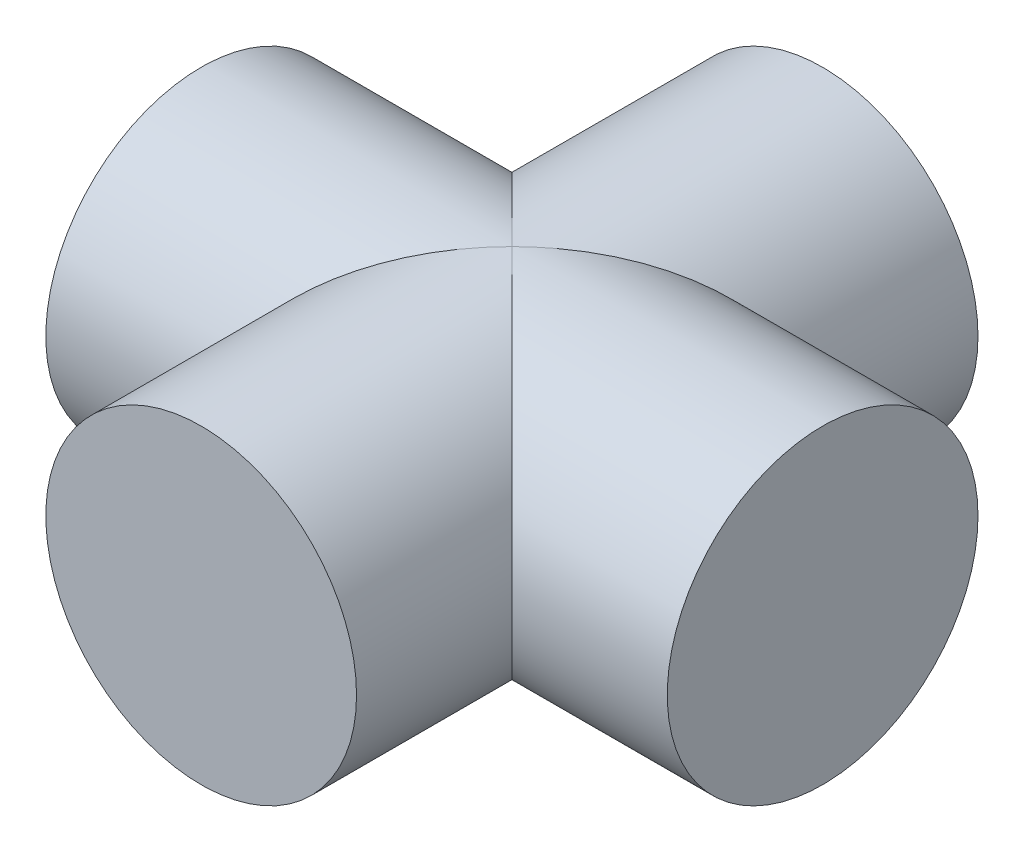
SolidWorks part; units mm, degrees
ref_plane "Front Plane" through (0, 0, 0) normal (0, 0, 1) x (1, 0, 0)
ref_plane "Top Plane" through (0, 0, 0) normal (0, 1, 0) x (1, 0, 0)
ref_plane "Right Plane" through (0, 0, 0) normal (1, 0, 0) x (0, 0, -1)
sketch "Sketch1" plane through (0, 0, 0) normal (0, 0, 1) x (1, 0, 0)
  circle A0 centre (0, 0) radius 5
extrude "Boss-Extrude1" add sketch "Sketch1" along normal blind 10 and the other way blind 10
sketch "Sketch2" plane through (0, 0, 0) normal (1, 0, 0) x (0, 0, -1)
  circle A0 centre (0, 0) radius 5
extrude "Boss-Extrude2" add sketch "Sketch2" along normal blind 10 and the other way blind 10
